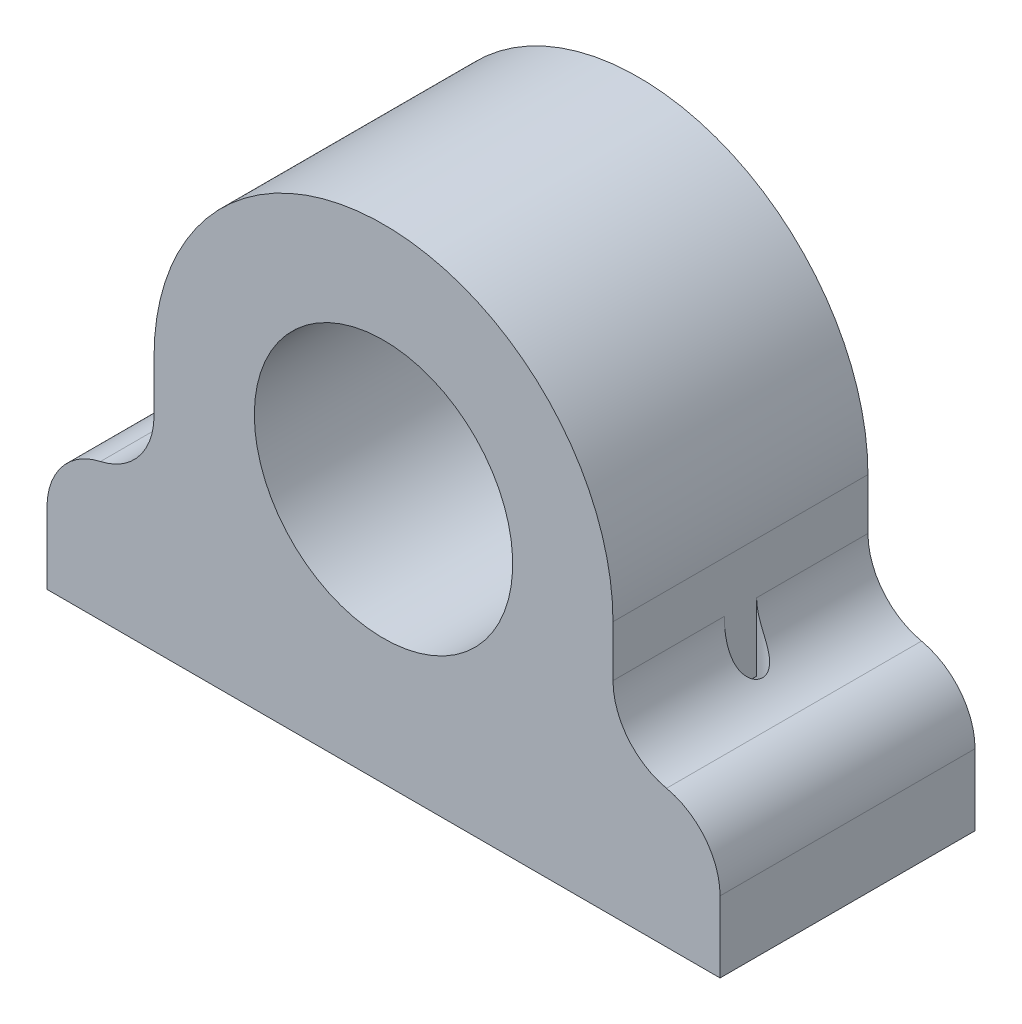
SolidWorks part; units mm, degrees
ref_plane "Front Plane" through (0, 0, 0) normal (0, 0, 1) x (1, 0, 0)
ref_plane "Top Plane" through (0, 0, 0) normal (0, 1, 0) x (1, 0, 0)
ref_plane "Right Plane" through (0, 0, 0) normal (1, 0, 0) x (0, 0, -1)
sketch "Sketch10" plane through (0, 0, 0) normal (0, 0, 1) x (1, 0, 0)
  line L0 (-8.5725, 0) -> (-8.5725, -4.445)
  line L1 (-8.5725, -4.445) -> (-18.7325, -4.445)
  line L2 (-18.7325, -4.445) -> (-18.7325, -9.525)
  line L3 (-18.7325, -9.525) -> (18.7325, -9.525)
  line L4 (18.7325, -9.525) -> (18.7325, -4.445)
  line L5 (18.7325, -4.445) -> (8.5725, -4.445)
  line L6 (8.5725, -4.445) -> (8.5725, 0)
  circle A0 centre (0, 0) radius 8.5725 construction
  circle A1 centre (0, 0) radius 6.4135 construction
  circle A2 centre (0, 0) radius 4.826 construction
  arc A3 (-8.5725, 0) -> (8.5725, 0) centre (0, 0) cw
  dimension "D1" = 17.145
  dimension "D2" = 12.827
  dimension "D3" = 9.652
  dimension "D4" = 10.16
  dimension "D5" = 5.08
  dimension "D6" = 4.445
extrude "Boss-Extrude1" add sketch "Sketch10" along normal blind 9.525
sketch "Sketch11" plane through (0, 0, 0) normal (0, 0, -1) x (-1, 0, 0)
  arc A0 (8.5725, 0) -> (-8.5725, 0) centre (0, 0) ccw construction
  arc A1 (8.5725, 0) -> (-8.5725, 0) centre (0, 0) ccw construction
  circle A2 centre (0, 0) radius 6.4135
  dimension "D1" = 12.827
extrude "Cut-Extrude7" cut sketch "Sketch11" against normal blind 1.5875
sketch "Sketch12" plane through (0, 0, 1.5875) normal (0, 0, -1) x (-1, 0, 0)
  circle A0 centre (0, 0) radius 4.826
  dimension "D1" = 9.652
extrude "Cut-Extrude8" cut sketch "Sketch12" against normal through all
sketch "Sketch13" plane through (0, -4.445, 0) normal (0, 1, 0) x (1, 0, 0)
  line L0 (-8.763, -4.7625) -> (-18.7325, -4.7625) construction
  line L1 (-18.7325, -9.525) -> (-18.7325, 0) construction
  line L2 (8.763, -4.7625) -> (18.7325, -4.7625) construction
  line L3 (18.7325, -9.525) -> (18.7325, 0) construction
  circle A0 centre (-8.763, -4.7625) radius 0.635
  circle A1 centre (8.763, -4.7625) radius 0.635
  dimension "D1" = 1.27
  dimension "D2" = 17.526
extrude "Cut-Extrude9" cut sketch "Sketch13" against normal through all
fillet "Fillet1" radius 2.54 4 edges at (18.7325, -4.445, 4.7625) (8.5725, -4.445, 2.0784) (-8.5725, -4.445, 7.4466) (-18.7325, -4.445, 4.7625)
sketch "Sketch15" plane through (0, -9.525, 0) normal (0, -1, 0) x (1, 0, 0)
  line L0 (-18.7325, 9.525) -> (-18.7325, 0) construction
  line L1 (-21.0457, 11.6569) -> (-12.573, 11.6569)
  line L2 (-21.0457, 11.6569) -> (-21.0457, -1.6668)
  line L3 (-21.0457, -1.6668) -> (-12.573, -1.6668)
  line L4 (-12.573, 11.6569) -> (-12.573, -1.6668)
  line L5 (-18.7325, 9.525) -> (18.7325, 9.525) construction
  line L6 (-18.7325, 0) -> (18.7325, 0) construction
  line L7 (18.7325, 9.525) -> (18.7325, 0) construction
  line L8 (12.573, 11.6569) -> (20.2347, 11.6569)
  line L9 (12.573, 11.6569) -> (12.573, -1.6668)
  line L10 (12.573, -1.6668) -> (20.2347, -1.6668)
  line L11 (20.2347, 11.6569) -> (20.2347, -1.6668)
  dimension "D1" = 6.1595
  dimension "D2" = 1.6668
  dimension "D3" = 2.1319
  dimension "D4" = 1.6668
  dimension "D5" = 2.1319
  dimension "D6" = 6.1595
  dimension "D7" = 8.4727
  dimension "D8" = 7.6617
extrude "Cut-Extrude10" cut sketch "Sketch15" against normal through all
fillet "Fillet2" radius 2.54 2 edges at (12.573, -4.445, 4.7625) (-12.573, -4.445, 4.7625)
equation "\"D5@Sketch15\"=\"D3@Sketch15\""
equation "\"D2@Sketch15\"=\"D4@Sketch15\""
equation "\"D6@Sketch15\"=\"D1@Sketch15\""
